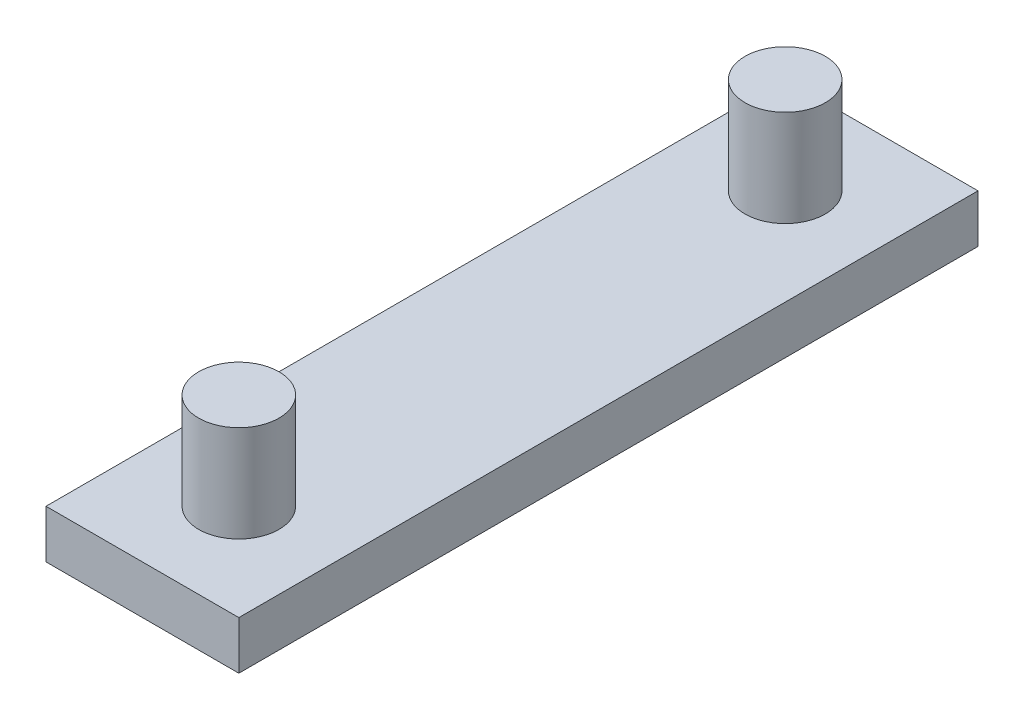
SolidWorks part; units mm, degrees
ref_plane "Front Plane" through (0, 0, 0) normal (0, 0, 1) x (1, 0, 0)
ref_plane "Top Plane" through (0, 0, 0) normal (0, 1, 0) x (1, 0, 0)
ref_plane "Right Plane" through (0, 0, 0) normal (1, 0, 0) x (0, 0, -1)
sketch "Sketch2" plane through (0, 0, 0) normal (0, 1, 0) x (1, 0, 0)
  line L1 (-6.1699, -22.8567) -> (5.8301, -22.8567)
  line L2 (-6.1699, -22.8567) -> (-6.1699, 23.1433)
  line L3 (-6.1699, 23.1433) -> (5.8301, 23.1433)
  line L4 (5.8301, -22.8567) -> (5.8301, 23.1433)
  dimension "D1" = 46
  dimension "D2" = 12
sketch "Sketch3" plane through (0, 0, 0) normal (0, 1, 0) x (1, 0, 0)
  line L2 (5.8301, -22.8567) -> (5.8301, 23.1433) construction
  line L4 (-6.1699, 23.1433) -> (5.8301, 23.1433) construction
  line L5 (5.8301, 0.1433) -> (-6.1699, 0.1433) construction
  line L6 (-6.1699, -22.8567) -> (-6.1699, 23.1433) construction
  circle A2 centre (-0.1699, 17.1433) radius 2.5
  circle A3 centre (-0.1699, -16.8567) radius 2.5
  dimension "D3" = 5
  dimension "D1" = 6
  dimension "D2" = 6
  dimension "D4" = 23
extrude "Boss-Extrude4" add sketch "Sketch3" along normal blind 9
extrude "Boss-Extrude5" add sketch "Sketch2" along normal blind 3
